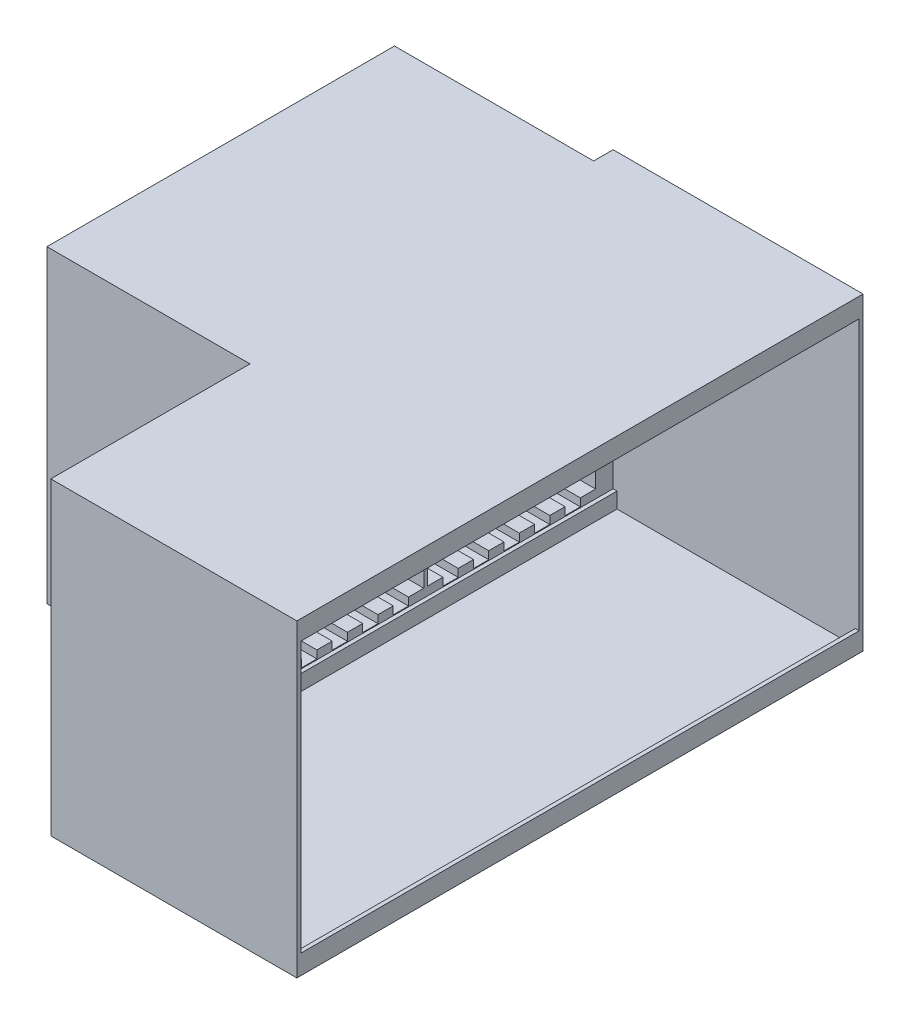
SolidWorks part; units mm, degrees
other "Исправление1"
sketch "Эскиз13" plane through (1050, -360, 1224.5) normal (0.916, -0.3443, 0.206) x (0.3981, 0.8438, -0.36)
ref_plane "Спереди" through (0, 0, 0) normal (0, 0, 1) x (1, 0, 0)
ref_plane "Сверху" through (0, 0, 0) normal (0, 1, 0) x (1, 0, 0)
ref_plane "Справа" through (0, 0, 0) normal (1, 0, 0) x (0, 0, -1)
other "Configuration Table"
sketch "Основа эскиз" plane through (0, 0, 0) normal (1, 0, 0) x (0, 0, -1)
  line L1 (-470, 395.98) -> (470, 395.98)
  line L2 (-470, 395.98) -> (-470, -395.98)
  line L3 (-470, -395.98) -> (470, -395.98)
  line L4 (470, 395.98) -> (470, -395.98)
  point P4 (0, 395.98)
  point P8 (-470, 0)
  dimension "D2" = 940
  dimension "D1" = 791.96
extrude "Основа" add sketch "Основа эскиз" along normal blind 1150
sketch "Вырез коретки эскиз" plane through (1150, 0, 0) normal (1, 0, 0) x (0, 0, -1)
  line L5 (470, 395.98) -> (-470, 395.98) construction
  line L6 (-470, 345.98) -> (460, 345.98)
  line L7 (-470, -395.98) -> (470, -395.98) construction
  line L8 (-470, 345.98) -> (-470, -345.98)
  line L9 (-470, -345.98) -> (460, -345.98)
  line L10 (460, 345.98) -> (460, -345.98)
  line L11 (-470, 395.98) -> (-470, -395.98) construction
  line L12 (470, -395.98) -> (470, 395.98) construction
  point P0 (0, 0)
  dimension "D3" = 10
  dimension "D4" = 50
extrude "Вырез коретки" cut sketch "Вырез коретки эскиз" against normal blind 630
sketch "вырез ячейки эскиз" plane through (520, 0, 0) normal (1, 0, 0) x (0, 0, -1)
  line L0 (460, 345.98) -> (-470, 345.98) construction
  line L1 (-455, 345.98) -> (-25, 345.98)
  line L2 (-455, 345.98) -> (-455, 25.98)
  line L3 (-455, 25.98) -> (-25, 25.98)
  line L4 (-25, 345.98) -> (-25, 25.98)
  line L17 (-470, 345.98) -> (-470, -345.98) construction
  dimension "D7" = 430
  dimension "D8" = 320
  dimension "D1" = 15
extrude "вырез ячейки" cut sketch "вырез ячейки эскиз" against normal blind 510
sketch "вырез двери эскиз" plane through (0, 0, 0) normal (-1, 0, 0) x (0, 0, 1)
  line L1 (25, 345.98) -> (460, 345.98)
  line L2 (25, 345.98) -> (25, 25.98)
  line L3 (25, 25.98) -> (460, 25.98)
  line L4 (460, 345.98) -> (460, 25.98)
  line L6 (455, 25.98) -> (25, 25.98) construction
  line L7 (25, 25.98) -> (25, 345.98) construction
  line L8 (455, 345.98) -> (455, 25.98) construction
  line L9 (455, 345.98) -> (455, 25.98) construction
  line L10 (25, 345.98) -> (455, 345.98) construction
  dimension "D2" = 5
extrude "вырез двери" cut sketch "вырез двери эскиз" against normal blind 10
sketch "Вырез основание низ эскиз" plane through (0, -345.98, 0) normal (0, 1, 0) x (1, 0, 0)
  line L0 (1150, -470) -> (1150, 460) construction
  line L1 (530, 460) -> (1140, 460)
  line L2 (530, 460) -> (530, -470)
  line L3 (530, -470) -> (1140, -470)
  line L4 (1140, 460) -> (1140, -470)
  line L5 (520, 460) -> (1150, 460) construction
  line L6 (520, -470) -> (1150, -470) construction
  dimension "D1" = 10
  dimension "D2" = 610
extrude "Вырез основание низ" cut sketch "Вырез основание низ эскиз" against normal blind 40
sketch "Вырез основания верх эскиз" plane through (0, 345.98, 0) normal (0, -1, 0) x (1, 0, 0)
  line L0 (520, 470) -> (1150, 470) construction
  line L1 (530, -460) -> (1140, -460)
  line L2 (530, -460) -> (530, 470)
  line L3 (530, 470) -> (1140, 470)
  line L4 (1140, -460) -> (1140, 470)
  line L5 (520, -460) -> (1150, -460) construction
  line L6 (1150, -460) -> (1150, 470) construction
  dimension "D1" = 10
  dimension "D2" = 610
extrude "Вырез основание верх" cut sketch "Вырез основания верх эскиз" against normal blind 40
sketch "вырез полозья эскиз" plane through (520, 0, 0) normal (1, 0, 0) x (0, 0, -1)
  line L0 (-455, 25.98) -> (-25, 25.98) construction
  line L1 (-415.9091, 25.98) -> (-376.8182, 25.98)
  line L2 (-415.9091, 25.98) -> (-415.9091, 5.98)
  line L3 (-415.9091, 5.98) -> (-376.8182, 5.98)
  line L4 (-376.8182, 25.98) -> (-376.8182, 5.98)
  dimension "D2" = 39.0909
  dimension "D3" = 39.0909
extrude "Вырез полозья" cut sketch "вырез полозья эскиз" against normal blind 510
pattern_linear "Линейный массив полозьев" count 5 spacing 78.1818 along (0, 0, -1) of "Вырез полозья"
pattern_linear "Линейный массив ячеек" count 2 spacing 440 along (0, 0, -1) count 2 spacing 350 along (0, -1, 0) of "Линейный массив полозьев", "вырез двери", "вырез ячейки"
sketch "Основание эскиз" plane through (0, 0, 470) normal (0, 0, 1) x (1, 0, 0)
  line L0 (1150, -395.98) -> (1150, -345.98)
  line L1 (1150, -345.98) -> (1140, -345.98)
  line L2 (1140, -345.98) -> (1140, -385.98)
  line L3 (1140, -385.98) -> (530, -385.98)
  line L4 (530, -385.98) -> (530, -345.98)
  line L5 (530, -345.98) -> (520, -345.98)
  line L6 (520, -345.98) -> (520, -395.98)
  line L7 (1150, -395.98) -> (0, -395.98) construction
  line L8 (520, -395.98) -> (1150, -395.98)
  line L9 (1140, 345.98) -> (1150, 345.98)
  line L10 (1150, 345.98) -> (1150, 395.98)
  line L11 (1150, 395.98) -> (520, 395.98)
  line L12 (1150, 395.98) -> (0, 395.98) construction
  line L13 (520, 395.98) -> (520, 345.98)
  line L14 (520, 345.98) -> (530, 345.98)
  line L15 (530, 345.98) -> (530, 385.98)
  line L16 (530, 385.98) -> (1140, 385.98)
  line L17 (1140, 385.98) -> (1140, 345.98)
extrude "Основание" add sketch "Основание эскиз" along normal blind 500
sketch "Стенка боквая эскиз" plane through (0, 0, 970) normal (0, 0, 1) x (1, 0, 0)
  line L1 (1150, 395.98) -> (520, 395.98)
  line L2 (1150, 395.98) -> (1150, -395.98)
  line L3 (1150, -395.98) -> (520, -395.98)
  line L4 (520, 395.98) -> (520, -395.98)
extrude "Стенка боковая" add sketch "Стенка боквая эскиз" along normal blind 10
sketch "Эскиз14" plane through (0, 0, -470) normal (0, 0, -1) x (-1, 0, 0)
  line L0 (-1150, 395.98) -> (0, 395.98) construction
  line L1 (0, -395.98) -> (-510, -395.98)
  line L2 (0, -395.98) -> (0, 395.98)
  line L3 (0, 395.98) -> (-510, 395.98)
  line L4 (-510, -395.98) -> (-510, 395.98)
  dimension "D1" = 510
extrude "Вырез-Вытянуть1" cut sketch "Эскиз14" against normal blind 50
equation "\"Ширина груза\"= 420"
equation "\"Глубина груза\"= 490"
equation "\"Высота груза\"= 297"
equation "\"Ширина ячейки\"= \"Ширина груза\" + 10"
equation "\"Глубина ячейки\"= \"Глубина груза\" + 10"
equation "\"Высота ячейки\"= \"Высота груза\" + 10 + 13"
equation "\"Колво ячеек ширина\"= 2"
equation "\"Колво ячеек высота\"= 2"
equation "\"Толщина стенки\"= 10"
equation "\"D2@Основа эскиз\"=( \"Ширина ячейки\" + \"Толщина стенки\" + \"Крепление дверцы\" ) * \"Колво ячеек ширина\" + \"Ширина пластины\""
equation "\"D1@Основа эскиз\"=( \"Высота ячейки\" + \"Толщина стенки\" + \"Высота пола\" ) * \"Колво ячеек высота\" + \"Отступ рейки\" * 2 + \"Высота рейки\" * 2 + \"Толщина стенки\" * 2 - 8.04"
equation "\"Крепление дверцы\"= 5"
equation "\"D7@вырез ячейки эскиз\"= \"Ширина ячейки\""
equation "\"D1@вырез ячейки эскиз\" = \"Толщина стенки\" + \"Крепление дверцы\""
equation "\"D8@вырез ячейки эскиз\"= \"Высота ячейки\""
equation "\"D2@вырез двери эскиз\"= \"Крепление дверцы\""
equation "\"D1@Основа\"=\"Глубина ячейки\" + \"Глубина каретки\" + \"Толщина стенки\" * 4 + \"Ширина рейки\" "
equation "\"D1@Вырез коретки\"=\"Глубина каретки\" + \"Толщина стенки\" * 2 + \"Ширина рейки\""
equation "\"D1@Вырез основание низ эскиз\"=\"Толщина стенки\" "
equation "\"Ширина рейки\"= \"Толщина шестерни\""
equation "\"D1@вырез ячейки\"= \"Глубина ячейки\" + \"Толщина стенки\""
equation "\"D1@вырез двери\"= \"Толщина стенки\""
equation "\"D2@Вырез основание низ эскиз\"=\"Глубина каретки\" + \"Ширина рейки\""
equation "\"Высота рейки\"= 20"
equation "\"D1@Вырез основания верх эскиз\"=\"Толщина стенки\""
equation "\"D2@Вырез основания верх эскиз\"=\"Глубина каретки\" + \"Ширина рейки\" "
equation "\"D1@Вырез основание верх\" = \"Высота рейки\" + \"Отступ рейки\""
equation "\"D4@Вырез коретки эскиз\"=\"Толщина стенки\"  + \"Высота рейки\" + \"Отступ рейки\""
equation "\"D1@Вырез коретки эскиз\"=\"Толщина стенки\" + \"Высота рейки\" + \"Отступ рейки\" "
equation "\"D3@Вырез коретки эскиз\" = \"Толщина стенки\""
equation "\"D1@Вырез основание низ\" = \"Высота рейки\" + \"Отступ рейки\""
equation "\"Высота пола\"= 20"
equation "\"Колво полозьев\"= 5"
equation "\"D1@вырез полозья эскиз\" = \"Высота пола\""
equation "\"D2@вырез полозья эскиз\" = \"Ширина ячейки\" /  ( \"Колво полозьев\" * 2 + 1 ) "
equation "\"D3@вырез полозья эскиз\"= \"Ширина ячейки\" / ( \"Колво полозьев\" * 2 + 1 )"
equation "\"D1@Вырез полозья\" = \"Глубина ячейки\" + \"Толщина стенки\""
equation "\"D1@Линейный массив полозьев\" = \"Колво полозьев\""
equation "\"D3@Линейный массив полозьев\" = \"Ширина ячейки\" /  ( \"Колво полозьев\" * 2 + 1 )  * 2"
equation "\"D1@Линейный массив ячеек\" = \"Колво ячеек ширина\""
equation "\"D2@Линейный массив ячеек\" = \"Колво ячеек высота\""
equation "\"D3@Линейный массив ячеек\" = \"Ширина ячейки\" + \"Толщина стенки\""
equation "\"D4@Линейный массив ячеек\" = \"Высота ячейки\" + \"Высота пола\" + \"Толщина стенки\""
equation "\"Отступ рейки\"= 20"
equation "\"Глубина каретки\"= \"Глубина ячейки\" + 30 + \"Мотор Y высота корпуса\" + 20"
equation "\"D1@Стенка боковая\" = \"Толщина стенки\""
equation "\"Длинна рейки\"= ( \"Ширина ячейки\" + \"Толщина стенки\" + \"Крепление дверцы\" ) * \"Колво ячеек ширина\" + \"Ширина ячейки выгрузки\" * \"Колво выгрузки\" + \"Толщина стенки\""
equation "\"D1@Основание\" = \"Длинна рейки\" -  ( \"Ширина ячейки\" + \"Толщина стенки\" + \"Крепление дверцы\" )  * \"Колво ячеек ширина\" - \"Толщина стенки\""
equation "\"Отступ шпильки\"= 20"
equation "\"Диаметр шпильки\"= 5"
equation "\"Длинна шпильки\"= ( \"Высота ячейки\" + \"Толщина стенки\" + \"Высота пола\" ) * \"Колво ячеек высота\" + ( \"Толщина стенки\" + \"Отступ рейки\" ) * 2 "
equation "\"Ширина пластины\"= 50  "
equation "\"Высота зона выгрузки\"= \"Высота ячейки\" * 2 + \"Толщина стенки\" * 2"
equation "\"Колво выгрузки\"= 1"
equation "\"D1@Эскиз14\"= \"Толщина стенки\" + \"Глубина ячейки\""
equation "\"D1@Вырез-Вытянуть1\"= \"Ширина пластины\""
equation "\"Ширина ячейки выгрузки\"= \"Ширина ячейки\" + \"Толщина стенки\" + \"Отступ крепления мотора фиксации\"*2"
equation "\"Отступ крепления мотора фиксации\" = 30"
